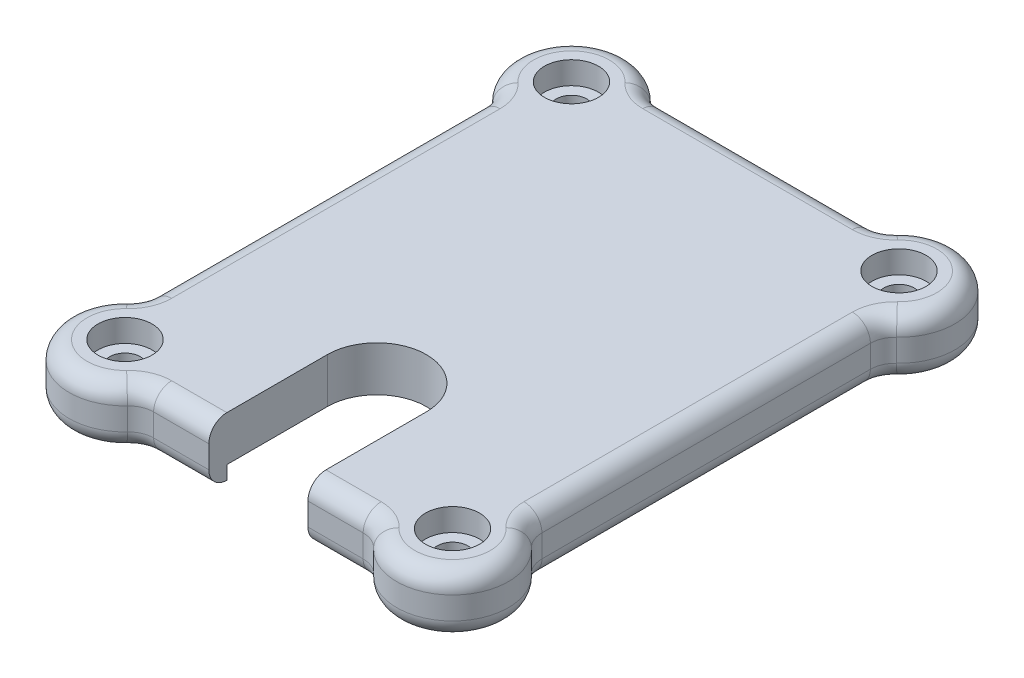
SolidWorks part; units mm, degrees
ref_plane "정면" through (0, 0, 0) normal (0, 0, 1) x (1, 0, 0)
ref_plane "윗면" through (0, 0, 0) normal (0, 1, 0) x (1, 0, 0)
ref_plane "우측면" through (0, 0, 0) normal (1, 0, 0) x (0, 0, -1)
sketch "스케치1" plane through (0, 0, 0) normal (0, 1, 0) x (1, 0, 0)
  line L0 (-19.35, -18.2277) -> (-19.35, 18.2277) construction
  line L1 (-15.35, -21.95) -> (15.35, -21.95) construction
  line L4 (15.35, -21.95) -> (15.35, 21.95) construction
  line L5 (-15.35, -21.95) -> (15.35, 21.95) construction
  line L6 (-15.35, 21.95) -> (15.35, -21.95) construction
  line L7 (-11.6277, 25.95) -> (11.6277, 25.95) construction
  line L10 (-15.35, 21.95) -> (-19.35, 25.95) construction
  line L11 (0, 0) -> (0, 51.1419) construction
  line L12 (-19.35, 25.95) -> (19.35, 25.95) construction
  line L13 (-19.35, -25.95) -> (-19.35, 25.95) construction
  line L14 (0, 0) -> (-42.6857, 0) construction
  line L15 (19.35, -18.2277) -> (19.35, 18.2277) construction
  line L16 (-15.35, 21.95) -> (15.35, 21.95) construction
  line L17 (-15.35, -21.95) -> (-15.35, 21.95) construction
  line L18 (19.35, -25.95) -> (19.35, 25.95) construction
  line L19 (-19.35, -25.95) -> (19.35, -25.95) construction
  line L20 (-11.6277, -25.95) -> (11.6277, -25.95) construction
  line L21 (-19.55, -18.2277) -> (-19.55, 18.2277)
  line L22 (-11.6277, -26.15) -> (11.6277, -26.15)
  line L23 (19.55, -18.2277) -> (19.55, 18.2277)
  line L24 (-11.6277, 26.15) -> (11.6277, 26.15)
  line L25 (-21.55, -18.2277) -> (-21.55, 18.2277)
  line L26 (-11.6277, 28.15) -> (11.6277, 28.15)
  line L27 (21.55, -18.2277) -> (21.55, 18.2277)
  line L28 (-11.6277, -28.15) -> (11.6277, -28.15)
  arc A0 (-15.267, 27.5213) -> (-20.9213, 21.867) centre (-18.1784, 24.7784) ccw construction
  arc A1 (-11.6277, 25.95) -> (-15.267, 27.5213) centre (-11.6277, 30.95) cw construction
  arc A2 (-19.35, 18.2277) -> (-20.9213, 21.867) centre (-24.35, 18.2277) ccw construction
  arc A3 (19.35, 18.2277) -> (20.9213, 21.867) centre (24.35, 18.2277) cw construction
  arc A4 (15.267, 27.5213) -> (20.9213, 21.867) centre (18.1784, 24.7784) cw construction
  arc A5 (11.6277, 25.95) -> (15.267, 27.5213) centre (11.6277, 30.95) ccw construction
  arc A6 (19.35, -18.2277) -> (20.9213, -21.867) centre (24.35, -18.2277) ccw construction
  arc A7 (11.6277, -25.95) -> (15.267, -27.5213) centre (11.6277, -30.95) cw construction
  arc A8 (15.267, -27.5213) -> (20.9213, -21.867) centre (18.1784, -24.7784) ccw construction
  arc A9 (-11.6277, -25.95) -> (-15.267, -27.5213) centre (-11.6277, -30.95) ccw construction
  arc A10 (-19.35, -18.2277) -> (-20.9213, -21.867) centre (-24.35, -18.2277) cw construction
  arc A11 (-15.267, -27.5213) -> (-20.9213, -21.867) centre (-18.1784, -24.7784) cw construction
  arc A12 (-15.1214, 27.6585) -> (-21.0585, 21.7214) centre (-18.1784, 24.7784) ccw
  arc A13 (-19.55, 18.2277) -> (-21.0585, 21.7214) centre (-24.35, 18.2277) ccw
  arc A14 (-19.55, -18.2277) -> (-21.0585, -21.7214) centre (-24.35, -18.2277) cw
  arc A15 (-15.1214, -27.6585) -> (-21.0585, -21.7214) centre (-18.1784, -24.7784) cw
  arc A16 (-11.6277, -26.15) -> (-15.1214, -27.6585) centre (-11.6277, -30.95) ccw
  arc A17 (11.6277, -26.15) -> (15.1214, -27.6585) centre (11.6277, -30.95) cw
  arc A18 (15.1214, -27.6585) -> (21.0585, -21.7214) centre (18.1784, -24.7784) ccw
  arc A19 (19.55, -18.2277) -> (21.0585, -21.7214) centre (24.35, -18.2277) ccw
  arc A20 (19.55, 18.2277) -> (21.0585, 21.7214) centre (24.35, 18.2277) cw
  arc A21 (15.1214, 27.6585) -> (21.0585, 21.7214) centre (18.1784, 24.7784) cw
  arc A22 (11.6277, 26.15) -> (15.1214, 27.6585) centre (11.6277, 30.95) ccw
  arc A23 (-11.6277, 26.15) -> (-15.1214, 27.6585) centre (-11.6277, 30.95) cw
  arc A24 (-11.6277, -28.15) -> (-13.6657, -29.03) centre (-11.6277, -30.95) ccw
  arc A25 (-13.6657, -29.03) -> (-22.43, -20.2657) centre (-18.1784, -24.7784) cw
  arc A26 (-21.55, -18.2277) -> (-22.43, -20.2657) centre (-24.35, -18.2277) cw
  arc A27 (-21.55, 18.2277) -> (-22.43, 20.2657) centre (-24.35, 18.2277) ccw
  arc A28 (-13.6657, 29.03) -> (-22.43, 20.2657) centre (-18.1784, 24.7784) ccw
  arc A29 (-11.6277, 28.15) -> (-13.6657, 29.03) centre (-11.6277, 30.95) cw
  arc A30 (11.6277, 28.15) -> (13.6657, 29.03) centre (11.6277, 30.95) ccw
  arc A31 (13.6657, 29.03) -> (22.43, 20.2657) centre (18.1784, 24.7784) cw
  arc A32 (21.55, 18.2277) -> (22.43, 20.2657) centre (24.35, 18.2277) cw
  arc A33 (21.55, -18.2277) -> (22.43, -20.2657) centre (24.35, -18.2277) ccw
  arc A34 (13.6657, -29.03) -> (22.43, -20.2657) centre (18.1784, -24.7784) ccw
  arc A35 (11.6277, -28.15) -> (13.6657, -29.03) centre (11.6277, -30.95) cw
  point P0 (0, 0)
  point P34 (0, 25.95)
  point P37 (19.35, 0)
  point P45 (-19.35, 0)
  dimension "D4" = 8
  dimension "D5" = 5
  dimension "D1" = 30.7
  dimension "D2" = 43.9
  dimension "D3" = 4
  dimension "D6" = 0.2
  dimension "D7" = 2
extrude "보스-돌출1" add sketch "스케치1" against normal blind 1.5
sketch "스케치2" plane through (0, 0, 0) normal (0, 1, 0) x (1, 0, 0)
  line L4 (-11.6277, -28.15) -> (11.6277, -28.15)
  line L5 (21.55, -18.2277) -> (21.55, 18.2277)
  line L6 (11.6277, 28.15) -> (-11.6277, 28.15)
  line L7 (-21.55, 18.2277) -> (-21.55, -18.2277)
  line L8 (-11.6277, -28.15) -> (11.6277, -28.15)
  line L9 (21.55, -18.2277) -> (21.55, 18.2277)
  line L10 (11.6277, 28.15) -> (-11.6277, 28.15)
  line L11 (-21.55, 18.2277) -> (-21.55, -18.2277)
  arc A12 (-11.6277, -28.15) -> (-13.6657, -29.03) centre (-11.6277, -30.95) ccw
  arc A13 (13.6657, -29.03) -> (11.6277, -28.15) centre (11.6277, -30.95) ccw
  arc A14 (13.6657, -29.03) -> (22.43, -20.2657) centre (18.1784, -24.7784) ccw
  arc A15 (21.55, -18.2277) -> (22.43, -20.2657) centre (24.35, -18.2277) ccw
  arc A16 (22.43, 20.2657) -> (21.55, 18.2277) centre (24.35, 18.2277) ccw
  arc A17 (22.43, 20.2657) -> (13.6657, 29.03) centre (18.1784, 24.7784) ccw
  arc A18 (11.6277, 28.15) -> (13.6657, 29.03) centre (11.6277, 30.95) ccw
  arc A19 (-13.6657, 29.03) -> (-11.6277, 28.15) centre (-11.6277, 30.95) ccw
  arc A20 (-13.6657, 29.03) -> (-22.43, 20.2657) centre (-18.1784, 24.7784) ccw
  arc A21 (-21.55, 18.2277) -> (-22.43, 20.2657) centre (-24.35, 18.2277) ccw
  arc A22 (-22.43, -20.2657) -> (-21.55, -18.2277) centre (-24.35, -18.2277) ccw
  arc A23 (-22.43, -20.2657) -> (-13.6657, -29.03) centre (-18.1784, -24.7784) ccw
  arc A24 (-11.6277, -28.15) -> (-13.6657, -29.03) centre (-11.6277, -30.95) ccw
  arc A25 (13.6657, -29.03) -> (11.6277, -28.15) centre (11.6277, -30.95) ccw
  arc A26 (13.6657, -29.03) -> (22.43, -20.2657) centre (18.1784, -24.7784) ccw
  arc A27 (21.55, -18.2277) -> (22.43, -20.2657) centre (24.35, -18.2277) ccw
  arc A28 (22.43, 20.2657) -> (21.55, 18.2277) centre (24.35, 18.2277) ccw
  arc A29 (22.43, 20.2657) -> (13.6657, 29.03) centre (18.1784, 24.7784) ccw
  arc A30 (11.6277, 28.15) -> (13.6657, 29.03) centre (11.6277, 30.95) ccw
  arc A31 (-13.6657, 29.03) -> (-11.6277, 28.15) centre (-11.6277, 30.95) ccw
  arc A32 (-13.6657, 29.03) -> (-22.43, 20.2657) centre (-18.1784, 24.7784) ccw
  arc A33 (-21.55, 18.2277) -> (-22.43, 20.2657) centre (-24.35, 18.2277) ccw
  arc A34 (-22.43, -20.2657) -> (-21.55, -18.2277) centre (-24.35, -18.2277) ccw
  arc A35 (-22.43, -20.2657) -> (-13.6657, -29.03) centre (-18.1784, -24.7784) ccw
  dimension "D1" = 0
extrude "보스-돌출2" add sketch "스케치2" along normal blind 5
sketch "스케치3" plane through (0, 5, 0) normal (0, 1, 0) x (1, 0, 0)
  circle A0 centre (-18.1784, 24.7784) radius 3
  circle A1 centre (18.1784, 24.7784) radius 3
  circle A2 centre (-18.1784, -24.7784) radius 3
  circle A3 centre (18.1784, -24.7784) radius 3
  dimension "D1" = 6
extrude "컷-돌출1" cut sketch "스케치3" against normal blind 2.5
sketch "스케치4" plane through (0, 2.5, 0) normal (0, 1, 0) x (1, 0, 0)
  circle A0 centre (-18.1784, 24.7784) radius 1.7
  circle A1 centre (18.1784, 24.7784) radius 1.7
  circle A2 centre (-18.1784, -24.7784) radius 1.7
  circle A3 centre (18.1784, -24.7784) radius 1.7
  dimension "D1" = 3.4
extrude "컷-돌출2" cut sketch "스케치4" against normal blind 3
fillet "필렛1" radius 2 32 edges at (-12.7377, -1.5, -28.3794) (0, -1.5, -28.15) (12.7377, -1.5, -28.3794) (22.5625, -1.5, -29.1625) (21.7794, -1.5, -19.3377) (21.55, -1.5, 0) (21.7794, -1.5, 19.3377) (22.5625, -1.5, 29.1625) (12.7377, -1.5, 28.3794) (0, -1.5, 28.15) (-12.7377, -1.5, 28.3794) (-22.5625, -1.5, 29.1625) (-21.7794, -1.5, 19.3377) (-21.55, -1.5, 0) (-21.7794, -1.5, -19.3377) (-12.7377, 5, -28.3794) (0, 5, -28.15) (12.7377, 5, -28.3794) (22.5625, 5, -29.1625) (21.7794, 5, -19.3377) (21.55, 5, 0) (21.7794, 5, 19.3377) (22.5625, 5, 29.1625) (12.7377, 5, 28.3794) (0, 5, 28.15) (-12.7377, 5, 28.3794) (-22.5625, 5, 29.1625) (-21.7794, 5, 19.3377) (-21.55, 5, 0) (-21.7794, 5, -19.3377) (-22.5625, -1.5, -29.1625) (-22.5625, 5, -29.1625)
sketch "스케치5" plane through (0, 5, 0) normal (0, 1, 0) x (1, 0, 0)
  line L0 (-5.5, -15) -> (-5.5, -29.304)
  line L1 (-5.5, -29.304) -> (5.5, -29.304)
  line L2 (5.5, -29.304) -> (5.5, -15)
  arc A0 (5.5, -15) -> (-5.5, -15) centre (0, -15) ccw
  dimension "D1" = 5.5
  dimension "D2" = 15
extrude "컷-돌출3" cut sketch "스케치5" against normal blind 7
